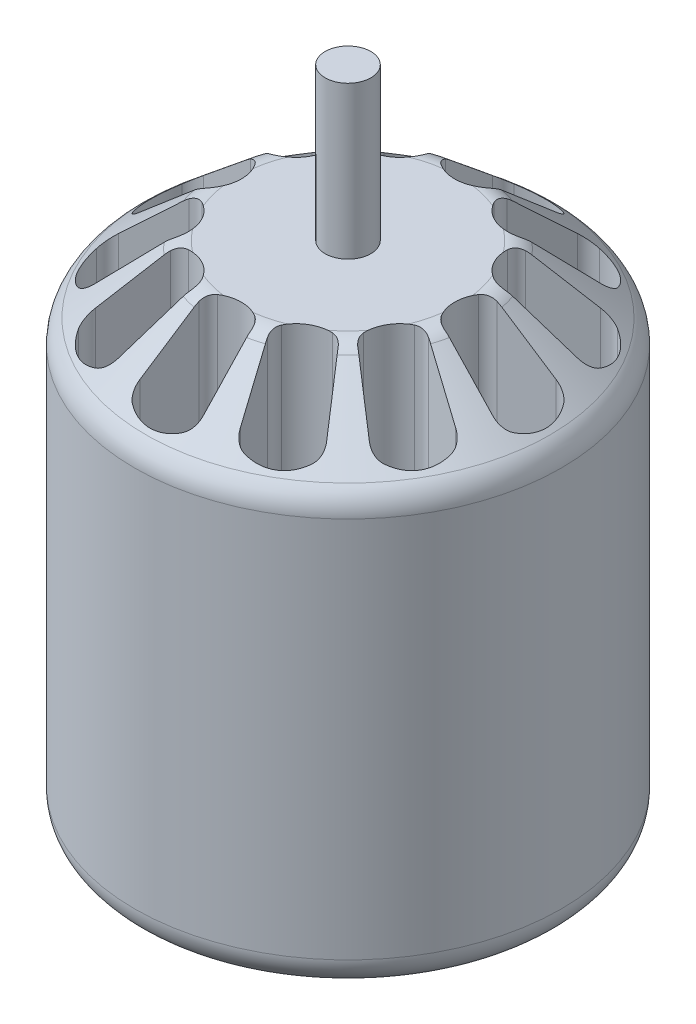
SolidWorks part; units mm, degrees
ref_plane "前基準面" through (0, 0, 0) normal (0, 0, 1) x (1, 0, 0)
ref_plane "上基準面" through (0, 0, 0) normal (0, 1, 0) x (1, 0, 0)
ref_plane "右基準面" through (0, 0, 0) normal (1, 0, 0) x (0, 0, -1)
sketch "草圖1" plane through (0, 0, 0) normal (0, 0, 1) x (1, 0, 0)
  line L0 (0, 35.3527) -> (0, -22.5832) construction
  line L1 (0, 33) -> (8, 33)
  line L2 (14, 28) -> (14, 0)
  line L3 (14, 0) -> (0, 0)
  line L4 (0, 33) -> (0, 0)
  line L5 (0, 0) -> (0.2147, 0.1182)
  line L6 (8, 33) -> (14, 28)
  dimension "D1" = 14
  dimension "D2" = 28
  dimension "D3" = 5
  dimension "D4" = 8
revolve "旋轉1" add sketch "草圖1" angle 360 about L0 region at (6.8322, 16.0022, 0)
fillet "圓角1" radius 2 3 edges at (-14, 0, 0) (-14, 28, 0) (-8, 33, 0)
sketch "草圖2" plane through (0, 33, 0) normal (0, 1, 0) x (1, 0, 0)
  line L0 (0, 0) -> (0, 13.2804) construction
  line L1 (-2.0747, 11.5735) -> (-1.6911, 8.0882)
  line L2 (-2.1336, 12.109) -> (2.1336, 12.109) construction
  line L3 (1.6911, 8.0882) -> (2.0747, 11.5735)
  line L4 (1.6464, 7.682) -> (-1.6464, 7.682) construction
  circle A0 centre (0, 0) radius 13.2804 construction
  circle A1 centre (0, 10) radius 3 construction
  arc A2 (-1.621, 12.5243) -> (1.621, 12.5243) centre (0, 10) cw
  arc A3 (-1.2219, 7.3464) -> (1.2219, 7.3464) centre (0, 9.3284) ccw
  arc A4 (-1.2219, 7.3464) -> (-1.6911, 8.0882) centre (-0.6971, 8.1976) cw
  arc A5 (1.2219, 7.3464) -> (1.6911, 8.0882) centre (0.6971, 8.1976) ccw
  arc A6 (1.621, 12.5243) -> (2.0747, 11.5735) centre (1.0807, 11.6829) cw
  arc A7 (-1.621, 12.5243) -> (-2.0747, 11.5735) centre (-1.0807, 11.6829) ccw
  dimension "D1" = 6
  dimension "D5" = 1
  dimension "D2" = 10
  dimension "D3" = 90
  dimension "D4" = 75
extrude "除料-伸長1" cut sketch "草圖2" against normal through all
ref_axis "基準軸1" through (0, 34.65, 0) along (0, -1, 0)
pattern_circular "環狀複製排列1" count 12 over 360 about axis through (0, 34.65, 0) along (0, -1, 0) of "除料-伸長1"
sketch "草圖3" plane through (0, 0, 0) normal (0, -1, 0) x (1, 0, 0)
  circle A0 centre (0, 0) radius 5
  dimension "D1" = 10
extrude "除料-伸長2" cut sketch "草圖3" against normal blind 2
sketch "草圖4" plane through (0, 33, 0) normal (0, 1, 0) x (1, 0, 0)
  circle A0 centre (0, 0) radius 1.5
  dimension "D1" = 3
extrude "填料-伸長1" add sketch "草圖4" along normal blind 10
